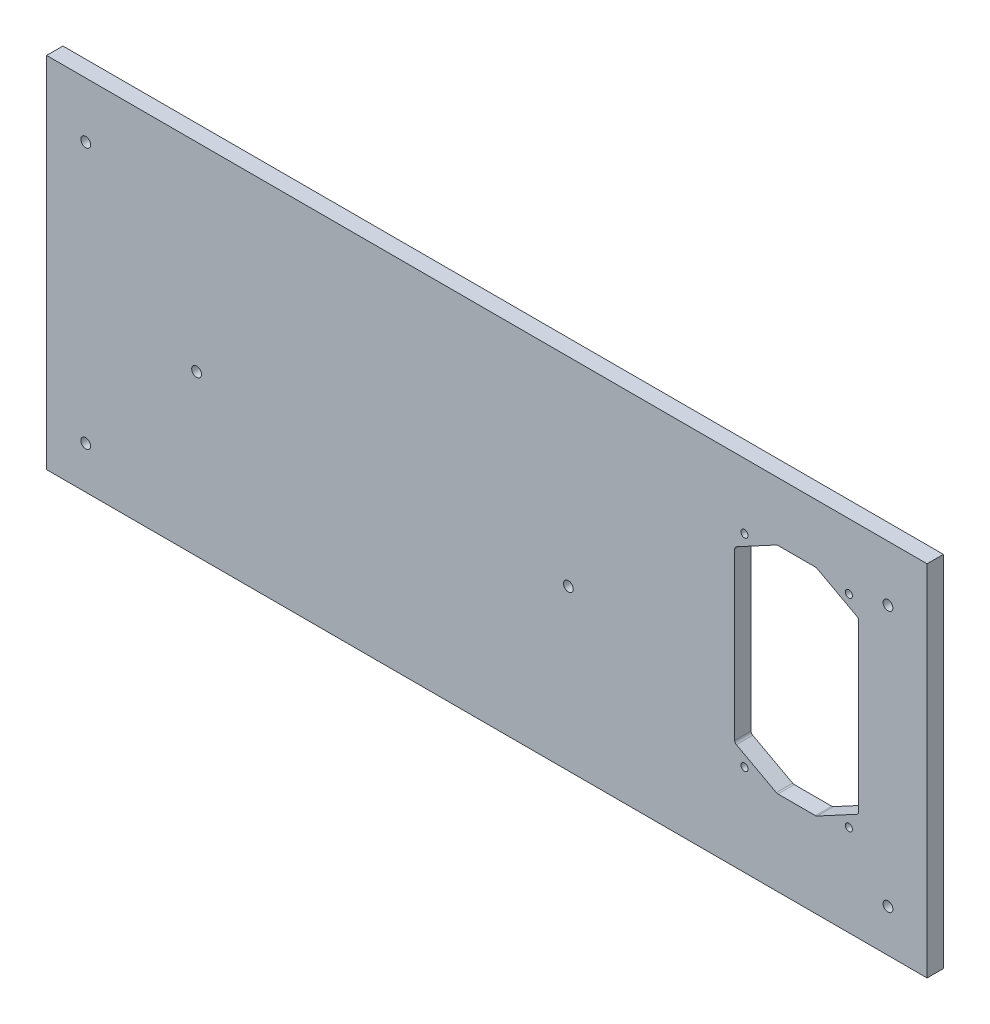
SolidWorks part; units mm, degrees
material "Acrylic (Medium-high impact)"
ref_plane "Front Plane" through (0, 0, 0) normal (0, 0, 1) x (1, 0, 0)
ref_plane "Top Plane" through (0, 0, 0) normal (0, 1, 0) x (1, 0, 0)
ref_plane "Right Plane" through (0, 0, 0) normal (1, 0, 0) x (0, 0, -1)
sketch "Sketch1" plane through (0, 0, 0) normal (0, 0, 1) x (1, 0, 0)
  line L1 (135, -55) -> (-135, -55)
  line L2 (135, -55) -> (135, 55)
  line L3 (135, 55) -> (-135, 55)
  line L4 (-135, -55) -> (-135, 55)
  line L5 (135, -55) -> (-135, 55) construction
  line L6 (135, 55) -> (-135, -55) construction
  point P0 (0, 0)
  dimension "D1" = 110
  dimension "D2" = 270
extrude "Base" add sketch "Sketch1" along normal mid plane 5
sketch "Sketch2" plane through (0, 0, 2.5) normal (0, 0, 1) x (1, 0, 0)
  line L0 (135, -55) -> (135, 55) construction
  line L1 (-135, -55) -> (135, -55) construction
  line L2 (-135, 55) -> (-135, -55) construction
  line L3 (135, 55) -> (-135, 55) construction
  circle A0 centre (-123, -42) radius 1.5
  circle A2 centre (123, -42) radius 1.5
  circle A3 centre (123, 38) radius 1.5
  circle A4 centre (-123, 38) radius 1.5
  dimension "D1" = 12
  dimension "D5" = 3
  dimension "D2" = 13
  dimension "D4" = 12
  dimension "D6" = 17
extrude "MountHoles" cut sketch "Sketch2" against normal through all
sketch "Sketch3" plane through (0, 0, -2.5) normal (0, 0, -1) x (-1, 0, 0)
  line L0 (-135, -55) -> (-135, 55) construction
  line L1 (135, -55) -> (-135, -55) construction
  circle A0 centre (-25, -6) radius 1.5
  circle A1 centre (89, -6) radius 1.5
  dimension "D4" = 3
  dimension "D1" = 114
  dimension "D2" = 110
  dimension "D3" = 49
extrude "MiddlePartHoles" cut sketch "Sketch3" against normal through all
chamfer "ChamferAll" distance 1.7 angle 45 6 edges at (-121.5, -42, -2.5) (124.5, -42, -2.5) (-121.5, 38, -2.5) (124.5, 38, -2.5) (-90.5, -6, -2.5) (23.5, -6, -2.5)
sketch "Sketch4" plane through (0, 0, -2.5) normal (0, 0, -1) x (-1, 0, 0)
  line L0 (-101, 37) -> (-114, 30)
  line L1 (-89, -29) -> (-101, -29)
  line L2 (-76, -22) -> (-76, 30)
  line L3 (-89, 37) -> (-101, 37)
  line L4 (-114, -22) -> (-114, 30)
  line L5 (-76, -29) -> (-114, 37) construction
  line L6 (-76, 37) -> (-114, -29) construction
  line L7 (-79, -27) -> (-111, -27) construction
  line L8 (-79, -27) -> (-79, 35) construction
  line L9 (-79, 35) -> (-111, 35) construction
  line L10 (-111, -27) -> (-111, 35) construction
  line L11 (-79, -27) -> (-111, 35) construction
  line L12 (-79, 35) -> (-111, -27) construction
  line L13 (-101, -29) -> (-114, -22)
  line L14 (-95, 4) -> (-95, 17.8562) construction
  line L15 (-76, 30) -> (-89, 37)
  line L16 (-76, -22) -> (-89, -29)
  line L17 (-135, -55) -> (-135, 55) construction
  line L18 (135, -55) -> (-135, -55) construction
  circle A0 centre (-79, 35) radius 1.1
  circle A1 centre (-111, 35) radius 1.1
  circle A2 centre (-111, -27) radius 1.1
  circle A3 centre (-79, -27) radius 1.1
  point P0 (-95, 4)
  point P14 (-95, 4)
  dimension "D1" = 2.2
  dimension "D2" = 62
  dimension "D3" = 32
  dimension "D4" = 38
  dimension "D5" = 66
  dimension "D6" = 13
  dimension "D7" = 7
  dimension "D8" = 13
  dimension "D9" = 7
  dimension "D10" = 7
  dimension "D11" = 13
  dimension "D12" = 13
  dimension "D13" = 7
  dimension "D14" = 40
  dimension "D15" = 59
extrude "Cut-Extrude1" cut sketch "Sketch4" against normal through all
fillet "Fillet1" radius 1 8 edges at (76, 30, 0) (89, -29, 0) (101, -29, 0) (114, -22, 0) (114, 30, 0) (101, 37, 0) (89, 37, 0) (76, -22, 0)
